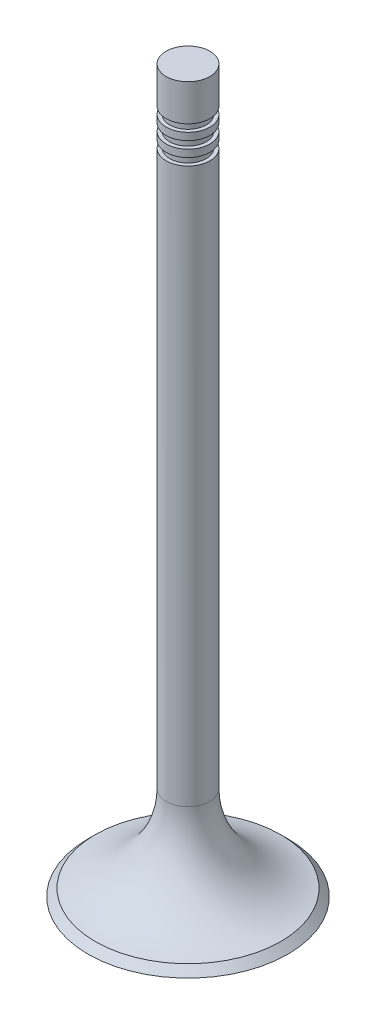
SolidWorks part; units mm, degrees
ref_plane "Front Plane" through (0, 0, 0) normal (0, 0, 1) x (1, 0, 0)
ref_plane "Top Plane" through (0, 0, 0) normal (0, 1, 0) x (1, 0, 0)
ref_plane "Right Plane" through (0, 0, 0) normal (1, 0, 0) x (0, 0, -1)
sketch "Sketch1" plane through (0, 0, 0) normal (0, 1, 0) x (1, 0, 0)
  circle A0 centre (0, 0) radius 13.7
  dimension "D1" = 27.4
extrude "Boss-Extrude1" add sketch "Sketch1" along normal blind 1
chamfer "Chamfer2" distance 1 angle 45 1 edges at (0, 1, 13.7)
sketch "Sketch4" plane through (0, 1, 0) normal (0, 1, 0) x (1, 0, 0)
  circle A0 centre (0, 0) radius 3
  dimension "D1" = 6
extrude "Boss-Extrude2" add sketch "Sketch4" along normal blind 97.8
fillet "Fillet1" radius 12 1 edges at (0, 1, 3)
sketch "Sketch5" plane through (0, 0, 0) normal (0, 0, 1) x (1, 0, 0)
  line L0 (0, 98.8) -> (0, 0) construction
  line L1 (3, 98.8) -> (-3, 98.8) construction
  line L2 (-3, 98.8) -> (-3, 93.8) construction
  line L3 (-3, 98.8) -> (-3, 12.7775) construction
  line L4 (-3, 93.8) -> (-3, 92.8)
  line L5 (-3, 92.8) -> (-3, 91.8)
  line L6 (-3, 91.8) -> (-3, 90.8)
  line L7 (-3, 90.8) -> (-3, 89.8)
  line L8 (-3, 89.8) -> (-3, 88.8)
  line L9 (-3, 88.8) -> (-3, 87.8)
  line L11 (-3, 93.8) -> (-2.5, 93.8)
  line L12 (-3, 93.8) -> (-3, 92.8)
  line L13 (-3, 92.8) -> (-2.5, 92.8)
  line L14 (-2.5, 93.8) -> (-2.5, 92.8)
  line L15 (-3, 91.8) -> (-2.5, 91.8)
  line L16 (-3, 91.8) -> (-3, 90.8)
  line L17 (-3, 90.8) -> (-2.5, 90.8)
  line L18 (-2.5, 91.8) -> (-2.5, 90.8)
  line L19 (-3, 89.8) -> (-2.5, 89.8)
  line L20 (-3, 89.8) -> (-3, 88.8)
  line L21 (-3, 88.8) -> (-2.5, 88.8)
  line L22 (-2.5, 89.8) -> (-2.5, 88.8)
  dimension "D1" = 5
  dimension "D2" = 1
  dimension "D3" = 1
  dimension "D4" = 1
  dimension "D5" = 1
  dimension "D6" = 1
  dimension "D7" = 1
  dimension "D8" = 0.5
revolve "Cut-Revolve1" cut sketch "Sketch5" angle 360 about L0 region at (-2.75, 93.3, 0) region at (-2.75, 89.3, 0) region at (-2.75, 91.3, 0)
